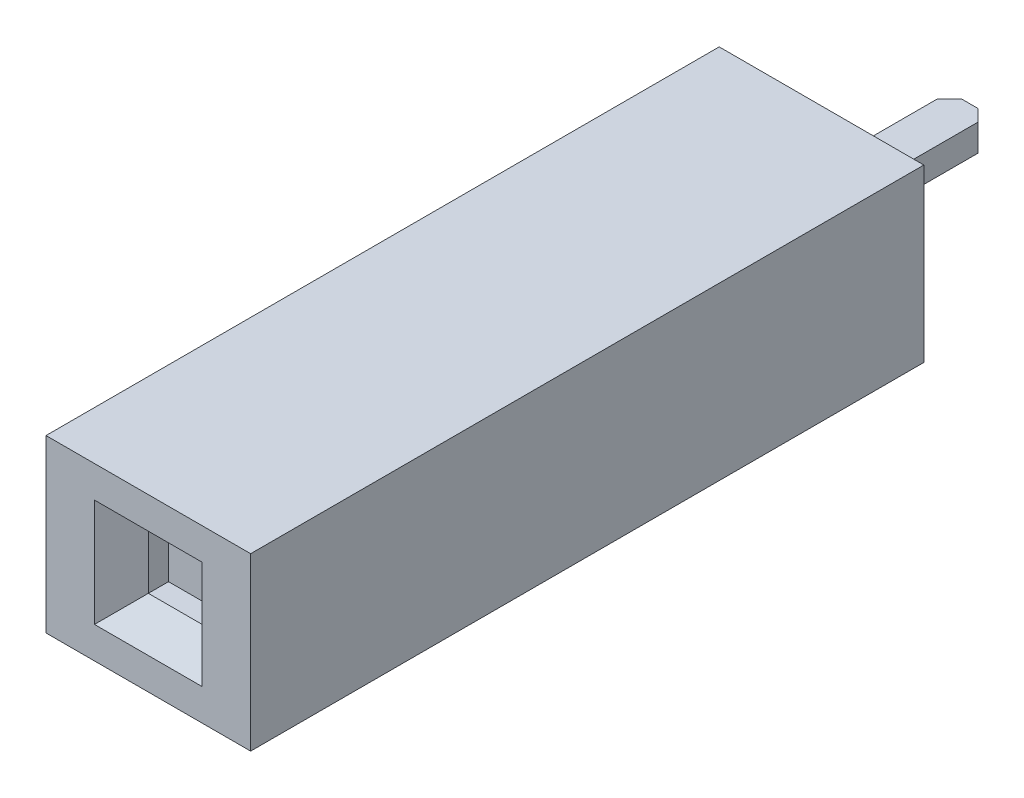
SolidWorks part; units mm, degrees
ref_plane "Front Plane" through (0, 0, 0) normal (0, 0, 1) x (1, 0, 0)
ref_plane "Top Plane" through (0, 0, 0) normal (0, 1, 0) x (1, 0, 0)
ref_plane "Right Plane" through (0, 0, 0) normal (1, 0, 0) x (0, 0, -1)
sketch "Sketch1" plane through (0, 0, 0) normal (1, 0, 0) x (0, -1, 0)
  line L1 (-1.27, 0) -> (1.27, 0)
  line L2 (-1.27, 0) -> (-1.27, -10)
  line L3 (-1.27, -10) -> (1.27, -10)
  line L4 (1.27, 0) -> (1.27, -10)
  line L5 (-1.27, 0) -> (1.27, -10) construction
  line L6 (-1.27, -10) -> (1.27, 0) construction
  point P0 (0, -5)
  point P6 (0, 0)
  dimension "D1" = 2.54
  dimension "D2" = 10
extrude "Boss-Extrude1" add sketch "Sketch1" along normal mid plane 3.04
sketch "Sketch2" plane through (0, 0, 10) normal (0, 0, 1) x (-1, 0, 0)
  line L0 (0, -1.27) -> (0, 1.27) construction
  line L3 (-1.52, -1.27) -> (1.52, -1.27) construction
  line L4 (-0.4, 0.4) -> (0.4, 0.4)
  line L5 (-0.4, 0.4) -> (-0.4, -0.4)
  line L6 (-0.4, -0.4) -> (0.4, -0.4)
  line L7 (0.4, 0.4) -> (0.4, -0.4)
  line L8 (-0.4, 0.4) -> (0.4, -0.4) construction
  line L9 (-0.4, -0.4) -> (0.4, 0.4) construction
  line L10 (-1.52, 1.27) -> (1.52, 1.27) construction
  point P5 (0, 0)
  dimension "D1" = 0.8
extrude "Cut-Extrude1" cut sketch "Sketch2" against normal blind 0.7
chamfer "Фаска1" distance 0.4 angle 45 4 edges at (-0.4, 0, 10) (0, -0.4, 10) (0.4, 0, 10) (0, 0.4, 10)
sketch "Sketch3" plane through (0, 0, 0) normal (0, 1, 0) x (1, 0, 0)
  line L0 (-0.3, 0) -> (-0.3, 2.0243)
  line L2 (-0.3, 2.0243) -> (-0.1243, 2.2)
  line L3 (-0.1243, 2.2) -> (0.1243, 2.2)
  line L4 (0, 2.2) -> (0, 0) construction
  line L5 (-0.3, 0) -> (0.3, 0)
  line L6 (0.3, 2.0243) -> (0.1243, 2.2)
  line L7 (0.3, 0) -> (0.3, 2.0243)
  dimension "D1" = 0.6
  dimension "D2" = 45
  dimension "D3" = 2.2
extrude "Boss-Extrude2" add sketch "Sketch3" along normal mid plane 0.4
equation "\"0.4Aмм\"=0.45"
